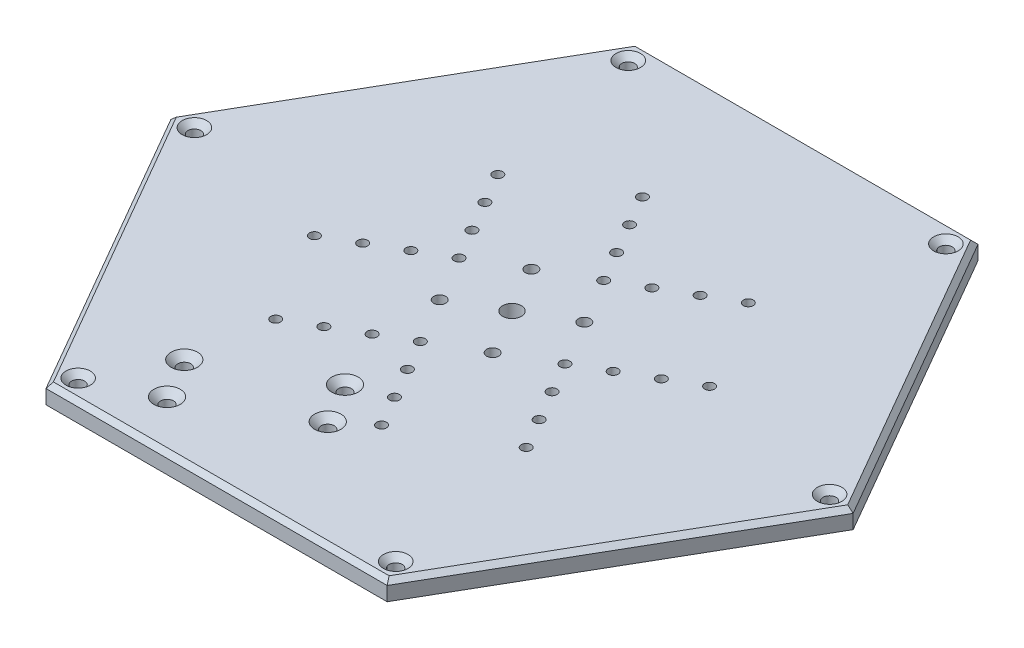
SolidWorks part; units mm, degrees
material "5052-H32"
ref_plane "Front Plane" through (0, 0, 0) normal (0, 0, 1) x (1, 0, 0)
ref_plane "Top Plane" through (0, 0, 0) normal (0, 1, 0) x (1, 0, 0)
ref_plane "Right Plane" through (0, 0, 0) normal (1, 0, 0) x (0, 0, -1)
sketch "Sketch1" plane through (0, 0, 0) normal (0, 1, 0) x (1, 0, 0)
  line L1 (72.5, 125.5737) -> (-72.5, 125.5737)
  line L2 (-72.5, 125.5737) -> (-145, 0)
  line L3 (-145, 0) -> (-72.5, -125.5737)
  line L4 (-72.5, -125.5737) -> (72.5, -125.5737)
  line L5 (72.5, -125.5737) -> (145, 0)
  line L6 (145, 0) -> (72.5, 125.5737)
  circle A0 centre (0, 0) radius 125.5737 construction
  dimension "D1" = 145
extrude "Boss-Extrude1" add sketch "Sketch1" along normal blind 8
sketch "Sketch10" plane through (0, 8, 0) normal (0, 1, 0) x (1, 0, 0)
  line L0 (145, 0) -> (0, 0) construction
  point P4 (135, 0)
  point P7 (67.5, -116.9134)
  point P8 (-67.5, -116.9134)
  point P9 (-135, 0)
  point P10 (-67.5, 116.9134)
  point P11 (67.5, 116.9134)
  point P12 (0, 0)
  dimension "D2" = 10
  dimension "D1" = 6
hole_wizard "CSK for M5 Flat Head Machine Screw2" positions "Sketch14" profile "Sketch13" countersink size "M5" standard "ANSI Metric"
sketch "Sketch14" plane through (0, 8, 0) normal (0, 1, 0) x (1, 0, 0)
  point P0 (-135, 0)
  point P3 (-67.5, -116.9134)
  point P6 (67.5, -116.9134)
  point P9 (135, 0)
  point P12 (67.5, 116.9134)
  point P15 (-67.5, 116.9134)
sketch "Sketch13" plane through (-135, 8, 0) normal (1, 0, 0) x (0, 0, 1)
  line L0 (0, 0) -> (0, 11.6524)
  line L1 (0, 11.6524) -> (2.75, 10)
  line L2 (2.75, 10) -> (2.75, 2.45)
  line L3 (2.75, 2.45) -> (5.2, 0)
  line L5 (5.2, 0) -> (0, 0)
  line L6 (-2.75, 2.45) -> (-5.2, 0) construction
  line L10 (0, 11.6524) -> (-2.75, 10) construction
  line L11 (0, -6.35) -> (0, 107.95) construction
  dimension "Hole Dia." = 5.5
  dimension "Hole Depth" = 10
  dimension "Near C'Sink Dia." = 10.4
  dimension "Near C'Sink Angle" = 90
  dimension "Drill Angle" = 118
chamfer "Chamfer4" distance 2 angle 45 6 edges at (0, 8, 125.5737) (108.75, 8, 62.7868) (108.75, 8, -62.7868) (0, 8, -125.5737) (-108.75, 8, -62.7868) (-108.75, 8, 62.7868)
sketch "Sketch15" plane through (0, 8, 0) normal (0, 1, 0) x (1, 0, 0)
  line L0 (0, 0) -> (107.0179, 61.7868) construction
  line L1 (142.6906, 0) -> (71.3453, 123.5737) construction
  line L2 (-30.7356, 8.2356) -> (-8.2356, -30.7356) construction
  line L3 (-30.7356, 8.2356) -> (8.2356, 30.7356) construction
  line L4 (-8.2356, -30.7356) -> (30.7356, -8.2356) construction
  line L5 (8.2356, 30.7356) -> (30.7356, -8.2356) construction
  line L6 (21.226, 38.2356) -> (43.726, -0.7356) construction
  line L7 (-11.25, 19.4856) -> (11.25, -19.4856) construction
  line L8 (34.2163, 45.7356) -> (56.7163, 6.7644) construction
  line L10 (47.2067, 53.2356) -> (69.7067, 14.2644) construction
  circle A0 centre (8.2356, 30.7356) radius 1.6 construction
  circle A1 centre (30.7356, -8.2356) radius 1.6 construction
  circle A2 centre (-8.2356, -30.7356) radius 1.6 construction
  circle A3 centre (-30.7356, 8.2356) radius 1.6 construction
  circle A4 centre (21.226, 38.2356) radius 1.6 construction
  circle A5 centre (43.726, -0.7356) radius 1.6 construction
  circle A6 centre (34.2163, 45.7356) radius 1.6 construction
  circle A7 centre (47.2067, 53.2356) radius 1.6 construction
  circle A8 centre (69.7067, 14.2644) radius 1.6 construction
  circle A9 centre (56.7163, 6.7644) radius 1.6 construction
  circle A10 centre (38.2356, -21.226) radius 1.6 construction
  circle A11 centre (45.7356, -34.2163) radius 1.6 construction
  circle A12 centre (53.2356, -47.2067) radius 1.6 construction
  circle A13 centre (14.2644, -69.7067) radius 1.6 construction
  circle A14 centre (6.7644, -56.7163) radius 1.6 construction
  circle A15 centre (-0.7356, -43.726) radius 1.6 construction
  circle A16 centre (-21.226, -38.2356) radius 1.6 construction
  circle A17 centre (-34.2163, -45.7356) radius 1.6 construction
  circle A18 centre (-47.2067, -53.2356) radius 1.6 construction
  circle A19 centre (-69.7067, -14.2644) radius 1.6 construction
  circle A20 centre (-56.7163, -6.7644) radius 1.6 construction
  circle A21 centre (-43.726, 0.7356) radius 1.6 construction
  circle A22 centre (-38.2356, 21.226) radius 1.6 construction
  circle A23 centre (-45.7356, 34.2163) radius 1.6 construction
  circle A24 centre (-53.2356, 47.2067) radius 1.6 construction
  circle A25 centre (-14.2644, 69.7067) radius 1.6 construction
  circle A26 centre (-6.7644, 56.7163) radius 1.6 construction
  circle A27 centre (0.7356, 43.726) radius 1.6 construction
  circle A28 centre (0, 0) radius 4.7625 construction
  circle A29 centre (19.4856, 11.25) radius 3.175 construction
  circle A30 centre (11.25, -19.4856) radius 3.175 construction
  circle A31 centre (-19.4856, -11.25) radius 3.175 construction
  circle A32 centre (-11.25, 19.4856) radius 3.175 construction
  point P16 (32.476, 18.75)
  point P18 (21.226, 38.2356)
  point P19 (43.726, -0.7356)
  point P23 (45.4663, 26.25)
  point P26 (58.4567, 33.75)
  point P71 (0, 0)
  point P81 (0, 0)
  dimension "D2" = 3.2
  dimension "D3" = 15
  dimension "D7" = 6.35
  dimension "D8" = 9.525
  dimension "D1" = 45
  dimension "D4" = 15
  dimension "D5" = 15
  dimension "D6" = 4
  dimension "D9" = 4
sketch "Sketch19" plane through (0, 8, 0) normal (0, -1, 0) x (1, 0, 0)
  line L0 (1.5942, 79.9086) -> (-41.7071, 104.9086) construction
  line L1 (-41.7071, 104.9086) -> (-51.7071, 87.5881) construction
  line L2 (-51.7071, 87.5881) -> (-8.4058, 62.5881) construction
  line L3 (-8.4058, 62.5881) -> (1.5942, 79.9086) construction
  line L4 (-20.0564, 92.4086) -> (-25.0564, 83.7484) construction
  line L5 (-25.0564, 83.7484) -> (-3.4058, 71.2484) construction
  line L6 (-25.0564, 83.7484) -> (-78.75, 114.7484) construction
  line L7 (-145, 0) -> (-72.5, 125.5737) construction
  dimension "D1" = 50
  dimension "D2" = 20
  dimension "D3" = 62
  dimension "D4" = 12.5
hole_wizard "CSK for M5 SFHCS1" positions "Sketch21" profile "Sketch22" countersink size "M5" standard "ANSI Metric"
sketch "Sketch21" plane through (0, 8, 0) normal (0, 1, 0) x (1, 0, 0)
  point P0 (1.5942, -79.9086)
  point P3 (-8.4058, -62.5881)
  point P6 (-51.7071, -87.5881)
  point P9 (-41.7071, -104.9086)
sketch "Sketch22" plane through (1.5942, 8, 79.9086) normal (1, 0, 0) x (0, 0, 1)
  line L0 (0, 0) -> (0, 11.6524)
  line L1 (0, 11.6524) -> (2.75, 10)
  line L2 (2.75, 10) -> (2.75, 2.85)
  line L3 (2.75, 2.85) -> (5.6, 0)
  line L5 (5.6, 0) -> (0, 0)
  line L6 (-2.75, 2.85) -> (-5.6, 0) construction
  line L10 (0, 11.6524) -> (-2.75, 10) construction
  line L11 (0, -6.35) -> (0, 107.95) construction
  dimension "Hole Dia." = 5.5
  dimension "Hole Depth" = 10
  dimension "Near C'Sink Dia." = 11.2
  dimension "Near C'Sink Angle" = 90
  dimension "Drill Angle" = 118
hole_wizard "M5x0.8 Tapped Hole1" positions "Sketch24" profile "Sketch23" tap size "M5x0.8" standard "ANSI Metric" end condition through all
sketch "Sketch24" plane through (0, 8, 0) normal (0, 1, 0) x (1, 0, 0)
  point P0 (47.2067, 53.2356)
  point P3 (69.7067, 14.2644)
  point P6 (56.7163, 6.7644)
  point P9 (34.2163, 45.7356)
  point P12 (21.226, 38.2356)
  point P15 (43.726, -0.7356)
  point P18 (38.2356, -21.226)
  point P21 (45.7356, -34.2163)
  point P24 (53.2356, -47.2067)
  point P27 (14.2644, -69.7067)
  point P30 (6.7644, -56.7163)
  point P33 (-0.7356, -43.726)
  point P36 (-8.2356, -30.7356)
  point P39 (-30.7356, 8.2356)
  point P42 (8.2356, 30.7356)
  point P45 (30.7356, -8.2356)
  point P48 (0.7356, 43.726)
  point P51 (-6.7644, 56.7163)
  point P54 (-14.2644, 69.7067)
  point P57 (-53.2356, 47.2067)
  point P60 (-45.7356, 34.2163)
  point P63 (-38.2356, 21.226)
  point P66 (-43.726, 0.7356)
  point P69 (-56.7163, -6.7644)
  point P72 (-69.7067, -14.2644)
  point P75 (-47.2067, -53.2356)
  point P78 (-34.2163, -45.7356)
  point P81 (-21.226, -38.2356)
sketch "Sketch23" plane through (47.2067, 8, -53.2356) normal (1, 0, 0) x (0, 0, 1)
  line L0 (0, 0) -> (0, 8)
  line L1 (0, 8) -> (2.1, 8)
  line L2 (2.1, 8) -> (2.1, 0)
  line L5 (2.1, 0) -> (0, 0)
  line L11 (0, -6.35) -> (0, 107.95) construction
  dimension "Thru Tap Drill Dia." = 4.2
  dimension "Thru Tap Drill Depth" = 8
cosmetic thread "Hole Thread1" parameters "D2"=5
cosmetic thread "Hole Thread2" parameters "D2"=5
cosmetic thread "Hole Thread3" parameters "D2"=5
cosmetic thread "Hole Thread4" parameters "D2"=5
cosmetic thread "Hole Thread5" parameters "D2"=5
cosmetic thread "Hole Thread6" parameters "D2"=5
cosmetic thread "Hole Thread7" parameters "D2"=5
cosmetic thread "Hole Thread8" parameters "D2"=5
cosmetic thread "Hole Thread9" parameters "D2"=5
cosmetic thread "Hole Thread10" parameters "D2"=5
cosmetic thread "Hole Thread11" parameters "D2"=5
cosmetic thread "Hole Thread12" parameters "D2"=5
cosmetic thread "Hole Thread13" parameters "D2"=5
cosmetic thread "Hole Thread14" parameters "D2"=5
cosmetic thread "Hole Thread15" parameters "D2"=5
cosmetic thread "Hole Thread16" parameters "D2"=5
cosmetic thread "Hole Thread17" parameters "D2"=5
cosmetic thread "Hole Thread18" parameters "D2"=5
cosmetic thread "Hole Thread19" parameters "D2"=5
cosmetic thread "Hole Thread20" parameters "D2"=5
cosmetic thread "Hole Thread21" parameters "D2"=5
cosmetic thread "Hole Thread22" parameters "D2"=5
cosmetic thread "Hole Thread23" parameters "D2"=5
cosmetic thread "Hole Thread24" parameters "D2"=5
cosmetic thread "Hole Thread25" parameters "D2"=5
cosmetic thread "Hole Thread26" parameters "D2"=5
cosmetic thread "Hole Thread27" parameters "D2"=5
cosmetic thread "Hole Thread28" parameters "D2"=5
hole_wizard "1/4-20 Tapped Hole1" positions "Sketch26" profile "Sketch25" tap size "1/4-20" standard "ANSI Inch" end condition through all
sketch "Sketch26" plane through (0, 8, 0) normal (0, 1, 0) x (1, 0, 0)
  point P0 (19.4856, 11.25)
  point P3 (-11.25, 19.4856)
  point P6 (-19.4856, -11.25)
  point P9 (11.25, -19.4856)
sketch "Sketch25" plane through (19.4856, 8, -11.25) normal (1, 0, 0) x (0, 0, 1)
  line L0 (0, 0) -> (0, 8)
  line L1 (0, 8) -> (2.5527, 8)
  line L2 (2.5527, 8) -> (2.5527, 0)
  line L5 (2.5527, 0) -> (0, 0)
  line L11 (0, -6.35) -> (0, 107.95) construction
  dimension "Thru Tap Drill Dia." = 5.1054
  dimension "Thru Tap Drill Depth" = 8
cosmetic thread "Hole Thread29" parameters "D2"=6.35
cosmetic thread "Hole Thread30" parameters "D2"=6.35
cosmetic thread "Hole Thread31" parameters "D2"=6.35
cosmetic thread "Hole Thread32" parameters "D2"=6.35
hole_wizard "3/8-16 Tapped Hole1" positions "Sketch28" profile "Sketch27" tap size "3/8-16" standard "ANSI Inch" end condition through all
sketch "Sketch28" plane through (0, 8, 0) normal (0, 1, 0) x (1, 0, 0)
  point P0 (0, 0)
sketch "Sketch27" plane through (0, 8, 0) normal (1, 0, 0) x (0, 0, 1)
  line L0 (0, 0) -> (0, 8)
  line L1 (0, 8) -> (3.9687, 8)
  line L2 (3.9687, 8) -> (3.9687, 0)
  line L5 (3.9687, 0) -> (0, 0)
  line L11 (0, -6.35) -> (0, 107.95) construction
  dimension "Thru Tap Drill Dia." = 7.9375
  dimension "Thru Tap Drill Depth" = 8
cosmetic thread "Hole Thread33" parameters "D2"=9.525
